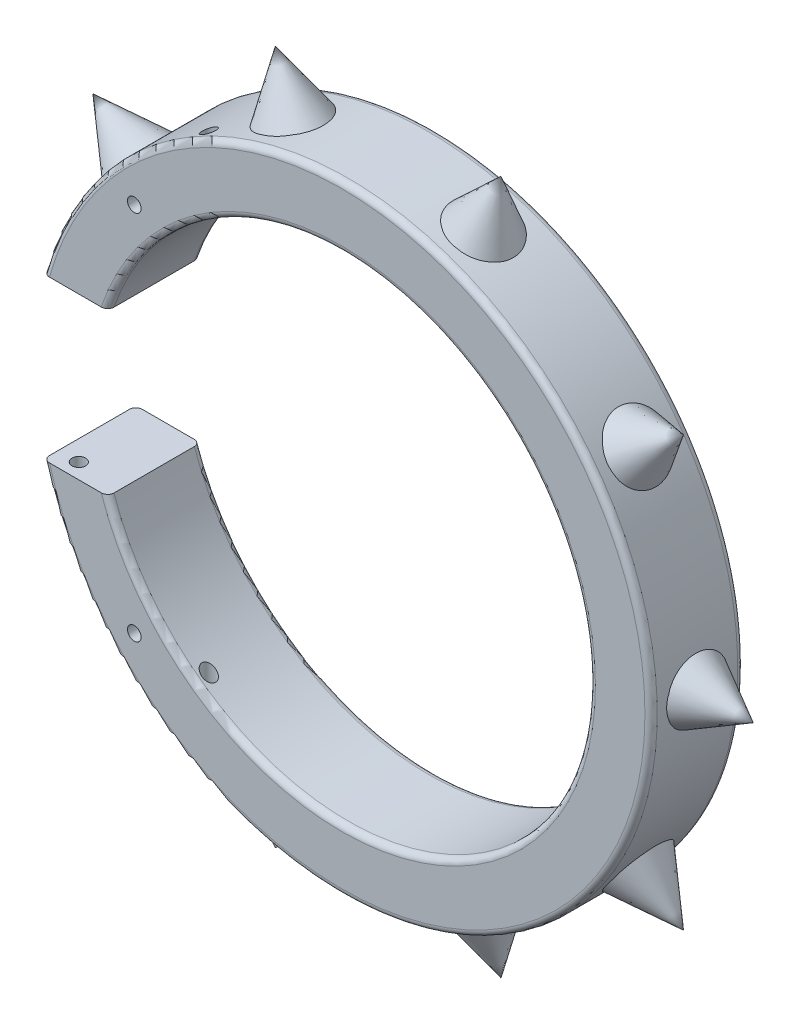
SolidWorks part; units mm, degrees
material "ABS"
ref_plane "正面" through (0, 0, 0) normal (0, 0, 1) x (1, 0, 0)
ref_plane "平面" through (0, 0, 0) normal (0, 1, 0) x (1, 0, 0)
ref_plane "右側面" through (0, 0, 0) normal (1, 0, 0) x (0, 0, -1)
sketch "ｽｹｯﾁ1" plane through (0, 0, 0) normal (0, 0, 1) x (1, 0, 0)
  circle A0 centre (0, 0) radius 50
  circle A1 centre (0, 0) radius 40
  dimension "D1" = 80
  dimension "1" = 100
extrude "ﾎﾞｽ - 押し出し1" add sketch "ｽｹｯﾁ1" along normal blind 15
fillet "ﾌｨﾚｯﾄ1" radius 1 4 edges at (50, 0, 15) (40, 0, 15) (40, 0, 0) (50, 0, 0)
sketch "ｽｹｯﾁ2" plane through (0, 0, 0) normal (0, 1, 0) x (1, 0, 0)
  line L0 (-59, -7.5) -> (-49, -2)
  line L1 (-49, -2) -> (-49, -7.5)
  line L3 (50, -1) -> (50, -14)
  line L4 (-50, -14) -> (-50, -1)
  line L5 (-50, -14) -> (-50, -11.55) construction
  line L6 (-59, -7.5) -> (-49, -7.5) construction
  line L7 (-61.7236, 0) -> (61.7236, 0) construction
  line L8 (-59, -7.5) -> (-49, -7.5)
  line L9 (-50, -7.5) -> (-50, -1) construction
  dimension "D1" = 7.5
  dimension "D2" = 2
  dimension "D3" = 10
  dimension "D4" = 5.5
revolve "回転1" add sketch "ｽｹｯﾁ2" angle 360 about L8
ref_axis "軸1" through (0, 0, -0.75) along (0, 0, 1)
pattern_circular "円形ﾊﾟﾀｰﾝ1" count 10 over 360 about axis through (0, 0, -0.75) along (0, 0, 1) of bodies 102
sketch "ｽｹｯﾁ3" plane through (0, 0, 0) normal (0, 1, 0) x (1, 0, 0)
  line L0 (-45, 0) -> (-45, -18.0596) construction
  line L1 (0, 0.75) -> (0, -15.75) construction
  line L2 (41, 0) -> (-41, 0) construction
  line L3 (-45, -12.5) -> (-19.4337, -12.5) construction
  circle A0 centre (-45, -12.5) radius 1.1
  circle A1 centre (-24, -12.5) radius 1.1
  dimension "D2" = 12.5
  dimension "D3" = 2.2
  dimension "D4" = 21
  dimension "D1" = 45
extrude "ｶｯﾄ - 押し出し1" cut sketch "ｽｹｯﾁ3" against normal through all and the other way through all
sketch "ｽｹｯﾁ4" plane through (0, 0, 0) normal (0, 0, -1) x (-1, 0, 0)
  line L0 (33.541, -30) -> (33.541, 30) construction
  circle A0 centre (0, 0) radius 45 construction
  circle A1 centre (33.541, -30) radius 1.1
  circle A2 centre (33.541, 30) radius 1.1
  dimension "D1" = 90
  dimension "D3" = 2.2
  dimension "D2" = 60
extrude "ｶｯﾄ - 押し出し2" cut sketch "ｽｹｯﾁ4" against normal through all
ref_plane "平面1" through (0, 13, 0) normal (0, 1, 0) x (1, 0, 0)
sketch "ｽｹｯﾁ5" plane through (0, 13, 0) normal (0, 1, 0) x (1, 0, 0)
  line L1 (-26.6711, -27.9757) -> (-73.0508, -27.9757)
  line L2 (-26.6711, -27.9757) -> (-26.6711, 12.8553)
  line L3 (-26.6711, 12.8553) -> (-73.0508, 12.8553)
  line L4 (-73.0508, -27.9757) -> (-73.0508, 12.8553)
extrude "ｶｯﾄ - 押し出し3" cut sketch "ｽｹｯﾁ5" against normal blind 26
